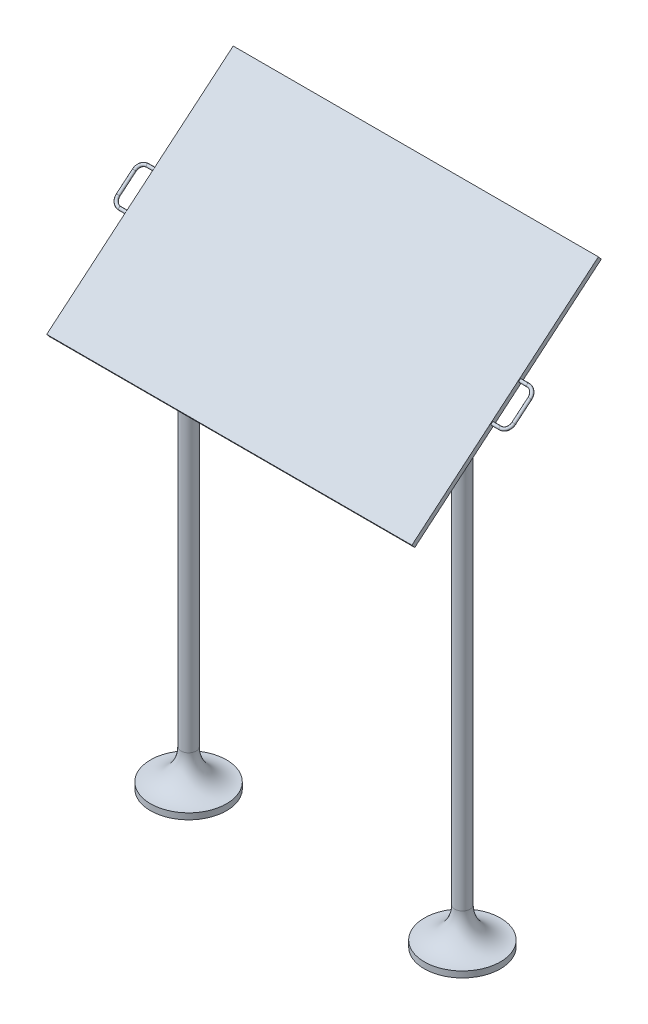
SolidWorks part; units mm, degrees
ref_plane "Alzado" through (0, 0, 0) normal (0, 0, 1) x (1, 0, 0)
ref_plane "Planta" through (0, 0, 0) normal (0, 1, 0) x (1, 0, 0)
ref_plane "Vista lateral" through (0, 0, 0) normal (1, 0, 0) x (0, 0, -1)
sketch "Croquis1" plane through (0, 0, 0) normal (0, 1, 0) x (1, 0, 0)
  line L0 (0, -26.677) -> (0, 24.609) construction
  circle A0 centre (-450, 0) radius 125
  circle A1 centre (450, 0) radius 125
  dimension "D1" = 250
  dimension "D2" = 900
extrude "Saliente-Extruir1" add sketch "Croquis1" along normal blind 20
sketch "Croquis2" plane through (0, 20, 0) normal (0, 1, 0) x (1, 0, 0)
  line L0 (0, -159.8314) -> (0, 176.8549) construction
  circle A0 centre (-450, 0) radius 25
  circle A1 centre (450, 0) radius 25
  dimension "D1" = 50
extrude "Saliente-Extruir2" add sketch "Croquis2" along normal blind 1623.09
fillet "Redondeo1" radius 100 1 edges at (-450, 20, 25)
fillet "Redondeo2" radius 100 1 edges at (450, 20, -25)
sketch "Croquis5" plane through (0, 0, 0) normal (1, 0, 0) x (0, 0, -1)
  line L0 (25, 1643.09) -> (-25, 1601.135)
  line L1 (-25, 1643.09) -> (-25, 120) construction
  line L3 (-25, 1601.135) -> (-25, 1643.09)
  line L4 (-25, 1643.09) -> (25, 1643.09)
  dimension "D1" = 40
extrude "Cortar-Extruir1" cut sketch "Croquis5" against normal through all and the other way through all
sketch "Croquis3" plane through (0, 0, 0) normal (1, 0, 0) x (0, 0, -1)
  line L0 (-306.4178, 1364.9975) -> (306.4178, 1879.2276)
  line L1 (306.4178, 1879.2276) -> (296.776, 1890.7182)
  line L2 (296.776, 1890.7182) -> (-316.0596, 1376.4881)
  line L3 (-316.0596, 1376.4881) -> (-306.4178, 1364.9975)
  line L4 (25, 1643.09) -> (-25, 1601.135) construction
  point P6 (0, 1622.1125)
  dimension "D1" = 800
  dimension "D2" = 15
extrude "Saliente-Extruir3" add sketch "Croquis3" along normal mid plane 1200 separate body
sketch "Croquis7" plane through (0, 951.8947, 798.7345) normal (0, 0.766, 0.6428) x (1, 0, 0)
  point P0 (450, 513.6018)
sketch "Croquis8" plane through (0, 951.8947, 798.7345) normal (0, 0.766, 0.6428) x (1, 0, 0)
  point P0 (-450, 513.6018)
sketch "Croquis9" plane through (600, 0, 0) normal (1, 0, 0) x (0, 0, -1)
  line L0 (-306.4178, 1364.9975) -> (306.4178, 1879.2276) construction
  line L1 (35.9604, 1671.8679) -> (45.6022, 1660.3773) construction
  line L2 (296.776, 1890.7182) -> (-316.0596, 1376.4881) construction
  circle A0 centre (40.7813, 1666.1226) radius 5
  point P4 (0, 1622.1125)
  dimension "D1" = 10
  dimension "D2" = 60
sketch "Croquis10" plane through (0, 963.3854, 808.3763) normal (0, 0.766, 0.6428) x (1, 0, 0)
  line L0 (600, 1102.2032) -> (625, 1102.2032)
  line L1 (600, 1097.2032) -> (600, 1107.2032) construction
  line L2 (650, 1077.2032) -> (650, 1008.1444)
  line L3 (625, 983.1444) -> (600, 983.1444)
  line L4 (600, 1442.6738) -> (600, 642.6738) construction
  line L5 (600, 1042.6738) -> (650, 1042.6738) construction
  arc A0 (625, 1102.2032) -> (650, 1077.2032) centre (625, 1077.2032) cw
  arc A1 (650, 1008.1444) -> (625, 983.1444) centre (625, 1008.1444) cw
  dimension "D1" = 25
  dimension "D2" = 50
sweep "Barrer1" add profiles "Croquis9" path "Croquis10"
mirror "Simetría1" about plane through (0, 0, 0) normal (1, 0, 0) of "Barrer1"
